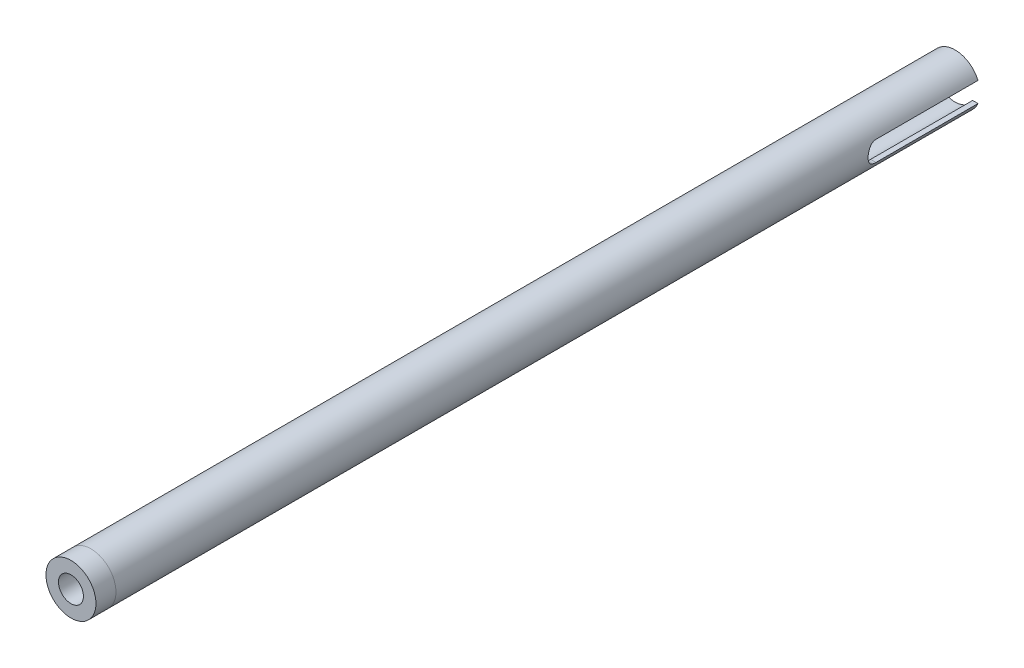
SolidWorks part; units mm, degrees
ref_plane "Front Plane" through (0, 0, 0) normal (0, 0, 1) x (1, 0, 0)
ref_plane "Top Plane" through (0, 0, 0) normal (0, 1, 0) x (1, 0, 0)
ref_plane "Right Plane" through (0, 0, 0) normal (1, 0, 0) x (0, 0, -1)
sketch "Axis" plane through (0, 0, 0) normal (0, 1, 0) x (1, 0, 0)
  line L0 (0, 0) -> (0, 280.7322) construction
  line L1 (0, 0) -> (0, -34.925) construction
  line L2 (0, 280.7322) -> (-7.9375, 280.7322) construction
  line L3 (0, 306.3781) -> (-28.8739, 213.0868) construction
  dimension "D1" = 34.925
  dimension "D2" = 7.9375
sketch "Sketch1" plane through (0, 0, 0) normal (0, 0, 1) x (1, 0, 0)
  line L0 (-7.9375, 0) -> (7.9375, 0) construction
  line L1 (-7.2748, 3.175) -> (7.2748, 3.175)
  line L2 (-7.2748, -3.175) -> (7.2748, -3.175)
  circle A0 centre (0, 0) radius 7.9375
  circle A1 centre (0, 0) radius 6.4135
  circle A2 centre (0, 0) radius 3.9688
  dimension "D1" = 15.875
  dimension "D3" = 7.9375
  dimension "D2" = 1.524
  dimension "D4" = 6.35
extrude "Threaded insert 1-1" add sketch "Sketch1" against normal blind 6.35 contours A2 L1 A1 | A1 L1 A0 | A2 L0 A1 L1 | A1 L0 A0 L1 | L0 A1 L2 A0 | L0 A2 L2 A1 | A2 L2 A1 | A1 L2 A0 | L0 A1 L2 A2 | L0 A0 L2 A1 | A0 L0 A1 L1 | A1 L0 A2 L1 region at (4.7887, 1.6543, 0) region at (4.7887, -1.6543, 0) region at (6.9234, 1.6163, 0) region at (6.9234, -1.6163, 0) region at (-4.7887, -1.6543, 0) region at (-4.7887, 1.6543, 0) region at (0, 4.6159, 0) region at (0, -4.6159, 0) region at (0, 6.5666, 0) region at (6.4237, -3.3281, 0) region at (-6.9234, -1.6163, 0) region at (-6.9234, 1.6163, 0)
extrude "Threaded insert 1-2" add sketch "Sketch1<3>" against normal blind 9.525 from surface contours A2 L1 A1 | A2 L0 A1 L1 | L0 A2 L2 A1 | A2 L2 A1 | L0 A1 L2 A2 | A1 L0 A2 L1 region at (4.7887, 1.6543, 0) region at (4.7887, -1.6543, 0) region at (-4.7887, -1.6543, 0) region at (-4.7887, 1.6543, 0) region at (0, 4.6159, 0) region at (0, -4.6159, 0) starting at face at (7.9375, 0, -6.35)
sketch "Sketch1<3>" plane through (0, 0, 0) normal (0, 0, 1) x (1, 0, 0) same geometry as "Sketch1"
extrude "A-arm tube" add sketch "Sketch1<4>" against normal up to vertex (280.7322 mm away) from surface separate body contours A1 L1 A0 | A1 L0 A0 L1 | L0 A1 L2 A0 | A1 L2 A0 | L0 A0 L2 A1 | A0 L0 A1 L1 region at (6.9234, 1.6163, 0) region at (6.9234, -1.6163, 0) region at (0, 6.5666, 0) region at (6.4237, -3.3281, 0) region at (-6.9234, -1.6163, 0) region at (-6.9234, 1.6163, 0) up to point (0, 0, -280.7322) starting at face at (6.4135, 0, -6.35)
sketch "Sketch1<4>" plane through (0, 0, 0) normal (0, 0, 1) x (1, 0, 0) same geometry as "Sketch1"
extrude "Apex slot" cut sketch "Sketch1<5>" along normal blind 35.56 from surface contours A0 L0 A1 L1 | L0 A0 L2 A1 | A1 L0 A0 L1 | L0 A1 L2 A0 region at (6.9234, 1.6163, 0) region at (6.9234, -1.6163, 0) region at (-6.9234, -1.6163, 0) region at (-6.9234, 1.6163, 0) starting at face at (6.4135, 0, -280.7322)
sketch "Sketch1<5>" plane through (0, 0, 0) normal (0, 0, 1) x (1, 0, 0) same geometry as "Sketch1"
fillet "Fillet1" radius 3.175 4 edges at (-6.4237, 3.175, -245.1722) (-6.4237, -3.175, -245.1722) (6.4237, -3.175, -245.1722) (6.4237, 3.175, -245.1722)
equation "\"tube diameter\"= 5 / 8"
equation "\"tube thickness\"= .06"
equation "\"apex thickness\"= .25"
equation "\"tube slot\"= 1.4"
equation "\"D1@Sketch1\"=\"tube diameter\""
equation "\"D2@Sketch1\"=\"tube thickness\""
equation "\"threaded insert hole\"= .3125"
equation "\"D3@Sketch1\"=\"threaded insert hole\""
equation "\"D4@Sketch1\"=\"apex thickness\""
equation "\"D1@Apex slot\" = \"tube slot\""
equation "\"D1@Fillet1\"=\"apex thickness\"/2"
equation "\"D2@Axis\"=\"tube diameter\"/2"
